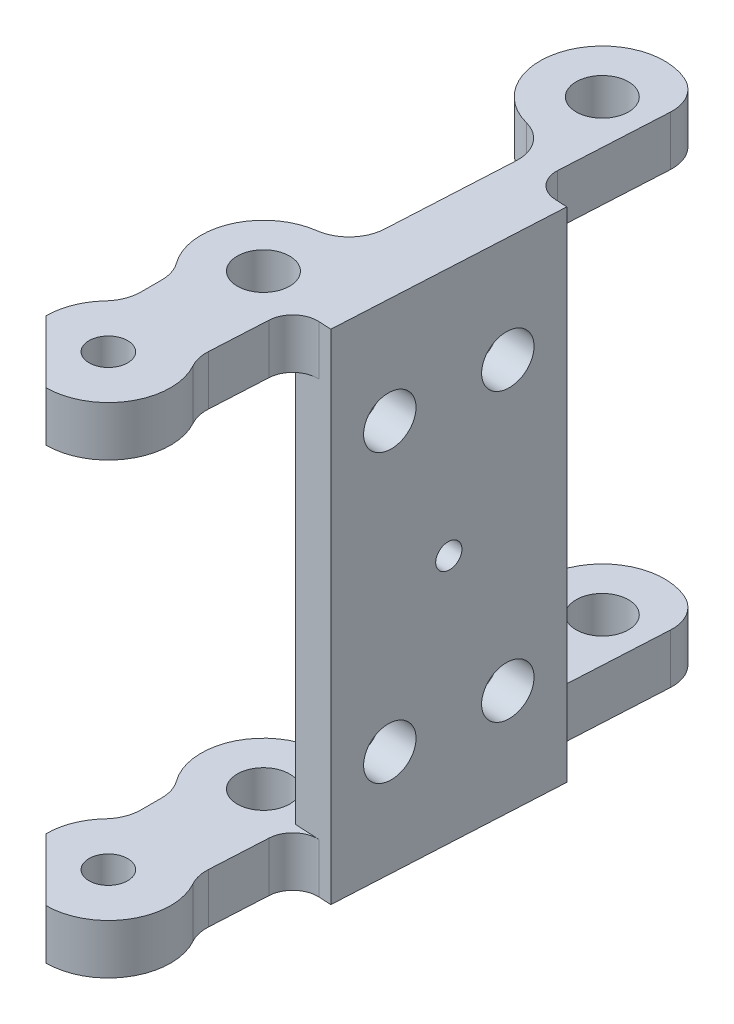
SolidWorks part; units mm, degrees
ref_plane "Front Plane" through (0, 0, 0) normal (0, 0, 1) x (1, 0, 0)
ref_plane "Top Plane" through (0, 0, 0) normal (0, 1, 0) x (1, 0, 0)
ref_plane "Right Plane" through (0, 0, 0) normal (1, 0, 0) x (0, 0, -1)
sketch "Sketch1" plane through (0, 0, 0) normal (0, 1, 0) x (1, 0, 0)
  line L0 (143.3333, 493) -> (716.6667, 493) construction
sketch "Sketch2" plane through (0, 0, 0) normal (0, 1, 0) x (1, 0, 0)
  line L0 (81.4722, 69.2986) -> (86.4722, 64.2986)
  line L1 (83.6263, 73.4096) -> (83.6263, 77.5229)
  line L2 (89.7299, 102.0349) -> (88.8636, 85.8025)
  line L7 (92.4509, 110.0003) -> (90.4247, 72.3609)
  line L8 (92.0481, 102.5189) -> (94.5466, 102.5189)
  line L9 (68.622, 64.6679) -> (68.8091, 64.6679)
  line L10 (82.0956, 50.9646) -> (82.0324, 51.0811)
  line L12 (94.5466, 102.5189) -> (93.4489, 82.1265)
  line L13 (94.0355, 93.0228) -> (93.4252, 81.6866)
  line L14 (93.4252, 81.6866) -> (90.9267, 81.6866)
  line L15 (47.4708, 107.3244) -> (47.5459, 107.4406)
  line L16 (50.5974, 103.1038) -> (50.7762, 103.3805)
  circle A0 centre (86.4722, 69.2986) radius 1.55
  arc A9 (88.8636, 85.8025) -> (83.6263, 77.5229) centre (87.0921, 81.1269) ccw
  arc A10 (83.6263, 73.4096) -> (81.4722, 69.2986) centre (86.4722, 69.2986) ccw
  arc A13 (92.4509, 110.0003) -> (89.7266, 101.9713) centre (88.5782, 106.8376) ccw
  arc A14 (86.4722, 64.2986) -> (90.4247, 72.3609) centre (86.4722, 69.2986) ccw
  circle A15 centre (87.0921, 81.1269) radius 2.1
  circle A18 centre (88.5782, 106.8376) radius 2.1
extrude "Boss-Extrude3" add sketch "Sketch2" along normal blind 4 contours L2 L7 A18 A15 A0 region at (87.7502, 0, -85.9738)
sketch "Sketch3" plane through (0, 4, 0) normal (0, 1, 0) x (1, 0, 0)
  line L0 (91.801, 97.9276) -> (90.8334, 79.9536)
  line L1 (91.801, 97.9276) -> (94.801, 97.7661)
  line L2 (90.8334, 79.9536) -> (93.8334, 79.7922)
  line L3 (94.801, 97.7661) -> (93.8334, 79.7922)
  line L4 (92.4509, 110.0003) -> (90.4247, 72.3609) construction
  dimension "D1" = 3
  dimension "D2" = 18
extrude "Boss-Extrude4" add sketch "Sketch3" against normal blind 40
ref_plane "Plane1" through (0, -16, 0) normal (0, 1, 0) x (1, 0, 0)
mirror "Mirror1" about plane through (0, -16, 0) normal (0, 1, 0) of "Boss-Extrude3"
fillet "Fillet1" radius 2 4 edges at (90.8334, -34, -79.9536) (90.8334, 2, -79.9536) (91.801, -34, -97.9276) (91.801, 2, -97.9276)
sketch "Sketch4" plane through (86.2794, 0, 4.6445) normal (-0.9986, 0, -0.0538) x (-0.0538, 0, 0.9986)
  line L0 (-84.7207, 0) -> (-89.2207, 0) construction
  line L1 (-102.7207, 0) -> (-84.7207, 0) construction
  line L2 (-89.2207, 0) -> (-89.2207, -4.5) construction
  line L3 (-93.7207, 0) -> (-93.7207, -7.4232) construction
  line L4 (-102.7207, -16) -> (-84.7207, -16) construction
  line L6 (-102.7207, -32) -> (-102.7207, 0) construction
  line L7 (-84.7207, -32) -> (-84.7207, 0) construction
  circle A0 centre (-89.2207, -4.5) radius 2
  circle A1 centre (-98.2207, -4.5) radius 2
  circle A2 centre (-89.2207, -27.5) radius 2
  circle A3 centre (-98.2207, -27.5) radius 2
  circle A4 centre (-93.7207, -16) radius 1
extrude "Cut-Extrude1" cut sketch "Sketch4" against normal blind 10
fillet "Fillet3" radius 3 10 edges at (92.4509, -34, -110.0003) (92.4509, 2, -110.0003) (90.4247, -34, -72.3609) (90.4247, 2, -72.3609) (89.7266, -34, -101.9713) (89.7266, 2, -101.9713) (83.6263, 2, -73.4096) (83.6263, 2, -77.5229) (83.6263, -34, -73.4096) (83.6263, -34, -77.5229)
fillet "Fillet4" radius 3 2 edges at (88.8636, -34, -85.8025) (88.8636, 2, -85.8025)
